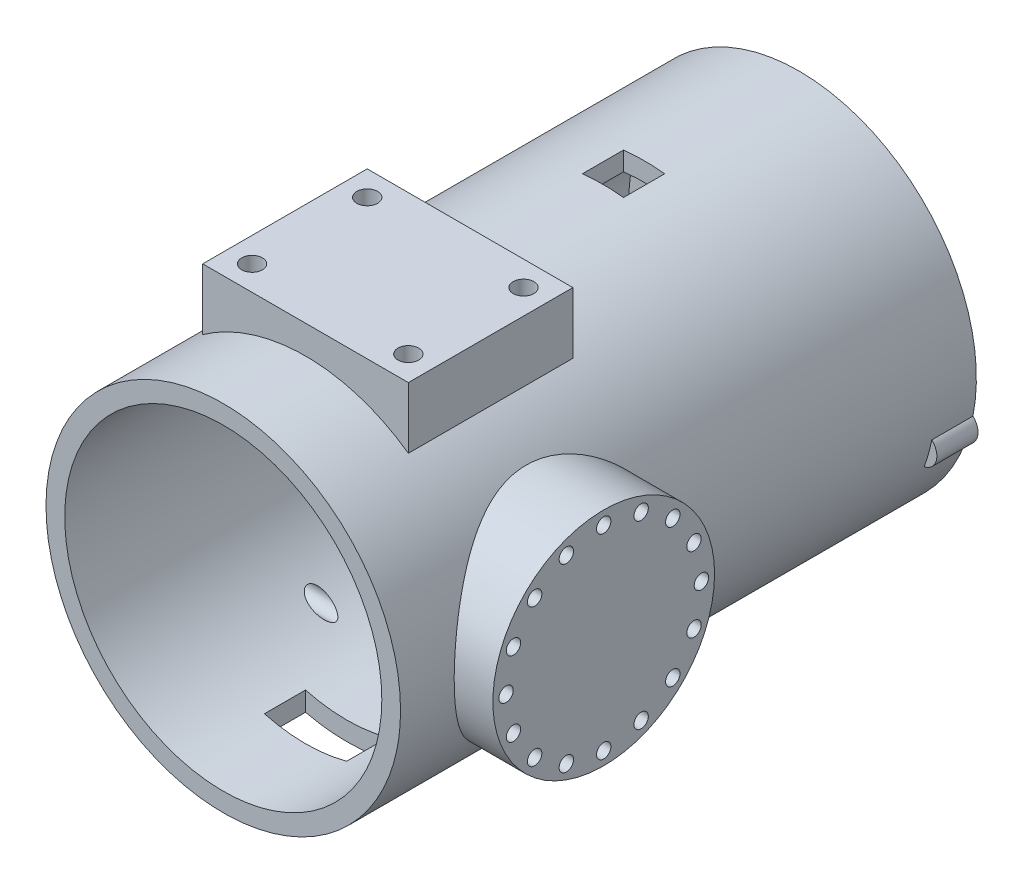
SolidWorks part; units mm, degrees
other "Markup1"
sketch "Sketch14" plane through (-43.1, 43.1, 140) normal (-0.1765, 0.0048, 0.9843) x (0.9842, -0.0149, 0.1765)
other "Markup2"
sketch "Sketch23" plane through (45.1, -43.1, 140) normal (0.9491, -0.0629, 0.3087) x (0.311, 0.031, -0.9499)
ref_plane "Front Plane" through (0, 0, 0) normal (0, 0, 1) x (1, 0, 0)
ref_plane "Top Plane" through (0, 0, 0) normal (0, 1, 0) x (1, 0, 0)
ref_plane "Right Plane" through (0, 0, 0) normal (1, 0, 0) x (0, 0, -1)
sketch "Sketch1" plane through (0, 0, 0) normal (0, 0, 1) x (1, 0, 0)
  circle A1 centre (0, 0) radius 43.1
  dimension "D1" = 86.2
extrude "Main Body" add sketch "Sketch1" along normal blind 140
ref_plane "Plane1" through (0, 43.1, 0) normal (0, 1, 0) x (1, 0, 0)
sketch "Sketch34" [suppressed] plane through (0, 43.1, 0) normal (0, 1, 0) x (1, 0, 0)
  line L6 (-5, -13) -> (5, -13)
  line L8 (-5, -13) -> (-5, -3)
  line L9 (-5, -3) -> (5, -3)
  line L10 (5, -13) -> (5, -3)
  line L11 (-5, -13) -> (5, -3) construction
  line L12 (-5, -3) -> (5, -13) construction
  point P0 (0, -8)
  dimension "D1" = 8
  dimension "D2" = 10
  dimension "D3" = 10
sketch "Sketch6" plane through (0, 43.1, 0) normal (0, 1, 0) x (1, 0, 0)
  line L2 (-5, -47.7) -> (5, -47.7)
  line L3 (-5, -47.7) -> (-5, -37.7)
  line L4 (-5, -37.7) -> (5, -37.7)
  line L5 (5, -47.7) -> (5, -37.7)
  line L6 (-5, -47.7) -> (5, -37.7) construction
  line L7 (-5, -37.7) -> (5, -47.7) construction
  point P2 (0, -42.7)
  dimension "D2" = 10
  dimension "D1" = 42.7
  dimension "D3" = 10
extrude "Cut-Extrude3" cut sketch "Sketch6" against normal through all
ref_plane "Plane2" through (52.5, 0, 0) normal (1, 0, 0) x (0, 0, -1)
sketch "Sketch8" plane through (52.5, 0, 0) normal (1, 0, 0) x (0, 0, -1)
  circle A0 centre (-100, 0) radius 26.95
  dimension "D1" = 53.9
  dimension "D2" = 100
extrude "Boss-Extrude2" add sketch "Sketch8" against normal blind 20
mirror "Mirror1" [suppressed] about plane through (0, 0, 0) normal (1, 0, 0)
ref_plane "Plane3" through (0, 50, 0) normal (0, 1, 0) x (1, 0, 0)
sketch "Sketch33" plane through (0, 50, 0) normal (0, 1, 0) x (1, 0, 0)
  line L1 (-25, -120) -> (25, -120)
  line L2 (-25, -120) -> (-25, -80)
  line L3 (-25, -80) -> (25, -80)
  line L4 (25, -120) -> (25, -80)
  line L5 (-25, -120) -> (25, -80) construction
  line L6 (-25, -80) -> (25, -120) construction
  point P0 (0, -100)
  dimension "D1" = 100
  dimension "D2" = 40
  dimension "D3" = 50
extrude "Boss-Extrude11" add sketch "Sketch33" against normal blind 22
sketch "Sketch35" plane through (0, 50, 0) normal (0, 1, 0) x (1, 0, 0)
  line L0 (-25, -120) -> (-25, -80) construction
  line L1 (25, -120) -> (25, -80) construction
  line L2 (25, -80) -> (-25, -80) construction
  line L3 (-25, -120) -> (25, -120) construction
  circle A0 centre (-19, -86) radius 2.525
  circle A1 centre (19, -86) radius 2.525
  circle A2 centre (-19, -114) radius 2.525
  circle A3 centre (19, -114) radius 2.525
  dimension "D1" = 5.05
  dimension "D2" = 6
  dimension "D3" = 6
  dimension "D4" = 6
  dimension "D5" = 6
extrude "Cut-Extrude14" cut sketch "Sketch35" against normal blind 4
sketch "Sketch5" plane through (0, 0, 140) normal (0, 0, 1) x (1, 0, 0)
  circle A0 centre (0, 0) radius 32
  dimension "D1" = 64
extrude "Hole 1" cut sketch "Sketch5" against normal through all
sketch "Sketch10" plane through (0, 0, 0) normal (0, 1, 0) x (1, 0, 0)
  line L0 (43.1, 0) -> (-43.1, 0) construction
  line L1 (-10, -120) -> (10, -120)
  line L2 (-10, -120) -> (-10, -110)
  line L3 (-10, -110) -> (10, -110)
  line L4 (10, -120) -> (10, -110)
  line L5 (-10, -120) -> (10, -110) construction
  line L6 (-10, -110) -> (10, -120) construction
  point P0 (0, -115)
  point P7 (-10, -115)
  dimension "D1" = 110
  dimension "D2" = 10
  dimension "D3" = 20
extrude "Motor Wire Hole" cut sketch "Sketch10" against normal through all
sketch "Sketch27" plane through (0, 0, 0) normal (1, 0, 0) x (0, 0, -1)
  line L1 (-100, -36.5) -> (-60, -36.5)
  line L2 (-100, -36.5) -> (-100, -27.5)
  line L3 (-100, -27.5) -> (-60, -27.5)
  line L4 (-60, -36.5) -> (-60, -27.5)
  dimension "D1" = 60
  dimension "D2" = 27.5
  dimension "D3" = 40
  dimension "D4" = 9
extrude "Boss-Extrude9" add sketch "Sketch27" along normal blind 33 and the other way blind 33
sketch "Sketch11" plane through (0, 0, 0) normal (1, 0, 0) x (0, 0, -1)
  circle A0 centre (-65, -32) radius 2.25
  circle A1 centre (-95, -32) radius 2.25
  dimension "D3" = 4.5
  dimension "D1" = 65
  dimension "D2" = 32
  dimension "D4" = 30
extrude "Cut-Extrude6" cut sketch "Sketch11" against normal through all both and the other way through all
sketch "Sketch28" plane through (-33, 0, 0) normal (-1, 0, 0) x (0, 0, 1)
  line L0 (62.8927, -28.35) -> (67.1073, -28.35)
  line L1 (67.1073, -28.35) -> (69.2147, -32)
  line L2 (69.2147, -32) -> (67.1073, -35.65)
  line L3 (67.1073, -35.65) -> (62.8927, -35.65)
  line L4 (62.8927, -35.65) -> (60.7853, -32)
  line L6 (60.7853, -32) -> (62.8927, -28.35)
  line L7 (92.8927, -28.35) -> (97.1073, -28.35)
  line L8 (97.1073, -28.35) -> (99.2147, -32)
  line L9 (99.2147, -32) -> (97.1073, -35.65)
  line L10 (97.1073, -35.65) -> (92.8927, -35.65)
  line L11 (92.8927, -35.65) -> (90.7853, -32)
  line L12 (90.7853, -32) -> (92.8927, -28.35)
  circle A0 centre (65, -32) radius 3.65 construction
  circle A1 centre (65, -32) radius 2.25 construction
  circle A2 centre (95, -32) radius 3.65 construction
  circle A3 centre (95, -32) radius 2.25 construction
  dimension "D2" = 7.3
extrude "Cut-Extrude7" cut sketch "Sketch28" against normal blind 3
sketch "Sketch29" plane through (33, 0, 0) normal (1, 0, 0) x (0, 0, -1)
  circle A0 centre (-95, -32) radius 3.6
  circle A1 centre (-65, -32) radius 3.6
  dimension "D1" = 7.2
extrude "Cut-Extrude8" cut sketch "Sketch29" against normal blind 4
sketch "Sketch2" plane through (0, 0, 140) normal (0, 0, 1) x (1, 0, 0)
  circle A0 centre (0, 0) radius 38.55
  dimension "D1" = 77.1
extrude "Cut-Extrude5" cut sketch "Sketch2" against normal blind 135
sketch "Sketch9" plane through (0, 0, 5) normal (0, 0, 1) x (1, 0, 0)
  circle A0 centre (0, 0) radius 38.1
  circle A1 centre (0, 0) radius 36.44
  dimension "D1" = 76.2
  dimension "D2" = 1.66
extrude "Boss-Extrude3" add sketch "Sketch9" along normal blind 10
extrude "Cut-Extrude13" [suppressed] cut sketch "Sketch34" against normal blind 15
sketch "Sketch30" plane through (52.5, 0, 0) normal (1, 0, 0) x (0, 0, -1)
  line L0 (-100, 23.75) -> (-100, 0) construction
  circle A0 centre (-100, 0) radius 23.75 construction
  circle A1 centre (-100, 23.75) radius 1.75
  circle A2 centre (-90.9113, 21.9421) radius 1.75
  circle A3 centre (-83.2062, 16.7938) radius 1.75
  circle A4 centre (-78.0579, 9.0887) radius 1.75
  circle A5 centre (-76.25, 0) radius 1.75
  circle A6 centre (-78.0579, -9.0887) radius 1.75
  circle A7 centre (-83.2062, -16.7938) radius 1.75
  circle A8 centre (-90.9113, -21.9421) radius 1.75
  circle A9 centre (-100, -23.75) radius 1.75
  circle A10 centre (-109.0887, -21.9421) radius 1.75
  circle A11 centre (-116.7938, -16.7938) radius 1.75
  circle A12 centre (-121.9421, -9.0887) radius 1.75
  circle A13 centre (-123.75, 0) radius 1.75
  circle A14 centre (-121.9421, 9.0887) radius 1.75
  circle A15 centre (-116.7938, 16.7938) radius 1.75
  circle A16 centre (-109.0887, 21.9421) radius 1.75
  point P38 (-100, 0)
  dimension "D1" = 47.5
  dimension "D2" = 3.5
  dimension "D3" = 16
extrude "Cut-Extrude9" cut sketch "Sketch30" against normal up to surface (22.1349 mm away) up to face at (21.4947, -32.0013, 97.25)
sketch "Sketch31" plane through (52.5, 0, 0) normal (1, 0, 0) x (0, 0, -1)
  line L0 (0, -43.1) -> (0, 43.1) construction
  line L1 (0, -15) -> (-10, -15)
  line L2 (0, -15) -> (0, -7.5)
  line L3 (0, -7.5) -> (-10, -7.5)
  line L4 (-10, -15) -> (-10, -7.5)
  dimension "D1" = 15
  dimension "D2" = 7.5
  dimension "D3" = 10
extrude "Boss-Extrude10" add sketch "Sketch31" against normal up to body from offset 9 offset against normal yes
sketch "Sketch32" plane through (0, 0, 0) normal (0, 0, -1) x (-1, 0, 0)
  line L0 (-43.5, -11.25) -> (-29.9573, -11.25) construction
  line L1 (-43.5, -15) -> (-43.5, -7.5) construction
  line L3 (-42.4424, -7.5) -> (-43.5, -7.5) construction
  line L5 (-43.5, -15) -> (-43.5, -7.5)
  line L6 (-43.5, -7.5) -> (-42.4424, -7.5)
  circle A0 centre (0, 0) radius 32 construction
  arc A2 (-40.4056, -15) -> (-42.4424, -7.5) centre (0, 0) ccw construction
  arc A3 (-40.4056, -15) -> (-42.2658, -8.4385) centre (-39.6806, -11.25) cw
  arc A4 (-42.2658, -8.4385) -> (-42.4424, -7.5) centre (0, 0) cw
  line M3 (-42.4424, -7.5) -> (-43.5, -7.5)
  line M4 (-43.5, -7.5) -> (-43.5, -15)
  line M5 (-43.5, -15) -> (-40.4056, -15)
extrude "Cut-Extrude10" cut sketch "Sketch32" against normal up to surface (10 mm away) contours M4 M3 | L5 M5 region at (43.0347, -8.5479, 0) region at (42.7123, -14.1508, 0) up to face at (42.5043, -11.2615, 10)
